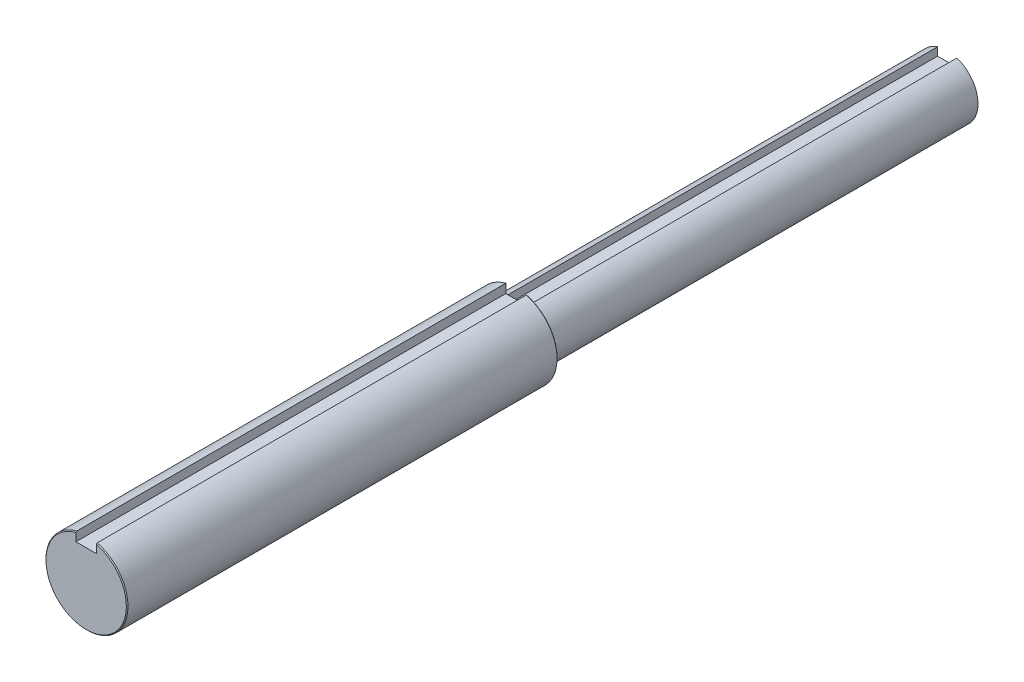
SolidWorks part; units mm, degrees
ref_plane "Front Plane" through (0, 0, 0) normal (0, 0, 1) x (1, 0, 0)
ref_plane "Top Plane" through (0, 0, 0) normal (0, 1, 0) x (1, 0, 0)
ref_plane "Right Plane" through (0, 0, 0) normal (1, 0, 0) x (0, 0, -1)
sketch "Sketch1" plane through (0, 0, 0) normal (1, 0, 0) x (0, 0, -1)
  line L0 (0, 0) -> (0, 12.7) construction
  line L1 (-304.8, 12.7) -> (304.8, 12.7)
  line L2 (-304.8, 12.7) -> (-304.8, -12.7)
  line L3 (-304.8, -12.7) -> (304.8, -12.7)
  line L4 (304.8, 12.7) -> (304.8, -12.7)
  line L5 (-304.8, 12.7) -> (304.8, -12.7) construction
  line L6 (-304.8, -12.7) -> (304.8, 12.7) construction
  line L7 (0, 0) -> (0, -12.7) construction
  point P0 (0, 0)
  point P8 (-275.59, 12.7)
  point P10 (275.59, 12.7)
  point P11 (-265.8533, -12.7)
  point P12 (271.0713, -12.7)
  dimension "Diameter" = 25.4
  dimension "Length" = 609.6
  dimension "D1" = 29.21
  dimension "D2" = 29.21
  dimension "D3" = 38.9467
  dimension "D4" = 33.7287
  dimension "Keyway Length" = 609.6
sketch "Sketch2" plane through (0, 0, 0) normal (0, 0, 1) x (1, 0, 0)
  line L0 (0, 0) -> (0, 12.7) construction
  line L2 (3.175, 9.525) -> (-3.175, 9.525)
  line L3 (3.175, 9.525) -> (3.175, 12.7)
  line L4 (3.175, 12.7) -> (-3.175, 12.7)
  line L5 (-3.175, 9.525) -> (-3.175, 12.7)
  line L6 (3.175, 9.525) -> (-3.175, 12.7) construction
  line L7 (3.175, 12.7) -> (-3.175, 9.525) construction
  circle A0 centre (0, 0) radius 12.7
  point P3 (0, 11.1125)
  point P10 (0, -12.7)
  dimension "D1" = 22.225
  dimension "Keyway Width" = 6.35
  dimension "Keyway Depth" = 3.175
sketch "Sketch3" plane through (0, 0, 0) normal (0, 0, 1) x (1, 0, 0)
  line L1 (-3.175, 9.525) -> (-3.175, 12.7) construction
  line L2 (3.175, 9.525) -> (-3.175, 9.525) construction
  line L3 (3.175, 9.525) -> (3.175, 12.7) construction
  line L5 (-3.175, 9.525) -> (-3.175, 12.2967)
  line L6 (3.175, 9.525) -> (-3.175, 9.525)
  line L7 (3.175, 9.525) -> (3.175, 12.2967)
  arc A1 (-3.175, 12.2967) -> (3.175, 12.2967) centre (0, 0) ccw
  circle A2 centre (0, 0) radius 12.7 construction
extrude "Boss-Extrude1" add sketch "Sketch3" along normal up to vertex (304.8 mm away) and the other way up to vertex (304.8 mm away) up to point (0, 12.7, 304.8) other way up to point (0, 12.7, -304.8)
chamfer "Chamfer1" distance 0.254 angle 45 2 edges at (0, -12.7, 304.8) (0, -12.7, -304.8)
ref_plane "Plane1" through (0, 0, 171.45) normal (0, 0, 1) x (1, 0, 0)
sketch "Sketch5" plane through (0, 0, 171.45) normal (0, 0, 1) x (1, 0, 0)
  circle A0 centre (0, 0) radius 9.525
  circle A1 centre (0, 0) radius 12.7
  dimension "D1" = 19.05
  dimension "D2" = 25.4
extrude "Cut-Extrude1" cut sketch "Sketch5" against normal through all
sketch "Sketch6" plane through (0, 0, 171.45) normal (0, 0, 1) x (1, 0, 0)
  line L0 (3.175, 9.525) -> (-3.175, 9.525) construction
  line L1 (-3, 12.525) -> (3, 12.525)
  line L2 (-3, 12.525) -> (-3, 6.525)
  line L3 (-3, 6.525) -> (3, 6.525)
  line L4 (3, 12.525) -> (3, 6.525)
  line L5 (-3, 12.525) -> (3, 6.525) construction
  line L6 (-3, 6.525) -> (3, 12.525) construction
  point P0 (0, 9.525)
  dimension "D1" = 6
  dimension "D2" = 6
extrude "Cut-Extrude2" cut sketch "Sketch6" against normal through all
chamfer "Chamfer2" distance 0.2 angle 45 8 edges at (-3, 7.7826, 171.45) (0, 6.525, 171.45) (3, 7.7826, 171.45) (0, -9.525, 171.45) (0, 9.525, 171.45) (3.175, 10.9109, 171.45) (-3.175, 10.9109, 171.45) (0, -12.7, 171.45)
ref_plane "Plane2" through (0, 0, 38.1) normal (0, 0, 1) x (1, 0, 0)
sketch "Sketch7" plane through (0, 0, 38.1) normal (0, 0, 1) x (1, 0, 0)
  circle A0 centre (0, 0) radius 63.5
  dimension "D1" = 127
extrude "Cut-Extrude3" cut sketch "Sketch7" against normal through all
equation "\"D2@Sketch1\"=1.15*\"Diameter@Sketch1\""
equation "\"D1@Sketch1\"=\"D2@Sketch1\""
equation "\"D3@Sketch1\"=\"D2@Sketch1\"*4/3"
equation "\"D4@Sketch1\"=\"D2@Sketch1\"/(tan(.5236*180/pi)*2)*4/3"
equation "\"D1@Chamfer1\"=\"Diameter@Sketch1\"*.01"
